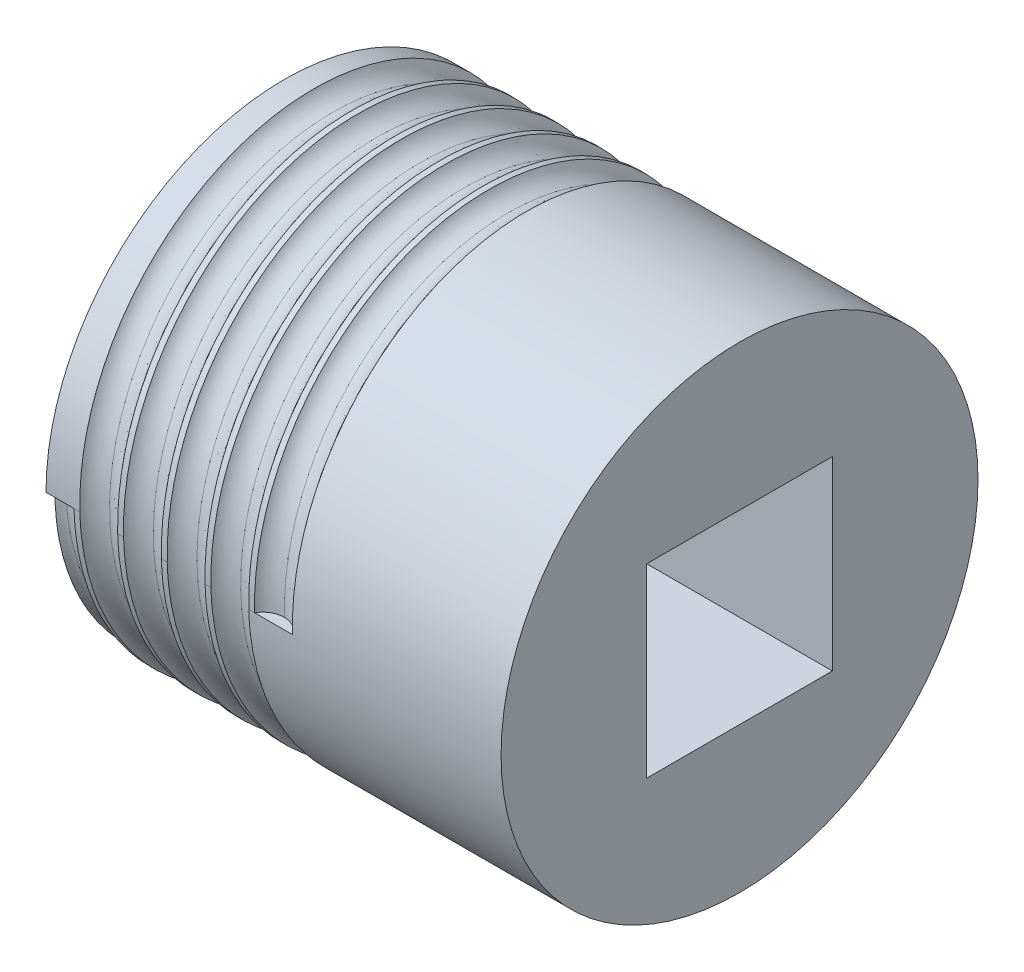
SolidWorks part; units mm, degrees
ref_plane "Front Plane" through (0, 0, 0) normal (0, 0, 1) x (1, 0, 0)
ref_plane "Top Plane" through (0, 0, 0) normal (0, 1, 0) x (1, 0, 0)
ref_plane "Right Plane" through (0, 0, 0) normal (1, 0, 0) x (0, 0, -1)
sketch "Sketch1" plane through (0, 0, 0) normal (1, 0, 0) x (0, 0, -1)
  line L1 (-3.2385, -3.2385) -> (3.2385, -3.2385)
  line L2 (-3.2385, -3.2385) -> (-3.2385, 3.2385)
  line L3 (-3.2385, 3.2385) -> (3.2385, 3.2385)
  line L4 (3.2385, -3.2385) -> (3.2385, 3.2385)
  line L5 (-3.2385, -3.2385) -> (3.2385, 3.2385) construction
  line L6 (-3.2385, 3.2385) -> (3.2385, -3.2385) construction
  circle A0 centre (0, 0) radius 8.3185
  dimension "D1" = 6.477
  dimension "D2" = 16.637
extrude "Boss-Extrude1" add sketch "Sketch1" along normal mid plane 15.875
sketch "Sketch2" plane through (0, 0, 0) normal (1, 0, 0) x (0, 0, -1)
  circle A0 centre (0, 0) radius 8.6995
  circle A2 centre (0, 0) radius 8.3185 construction
  dimension "D1" = 0.381
curve "Helix/Spiral1" pitch 1.524 height 7.62 radius 8.6995 centre (0, 0, 0) axis (-1, 0, 0) start towards (0, 0, 1)
sketch "Sketch3" plane through (0, 0, 0) normal (0, 1, 0) x (1, 0, 0)
  circle A0 centre (0, -8.6995) radius 0.762
  point P2 (0, 0)
  dimension "D1" = 1.524
sweep "Cut-Sweep1" cut profiles "Sketch3" path "Helix/Spiral1" align with end faces yes
